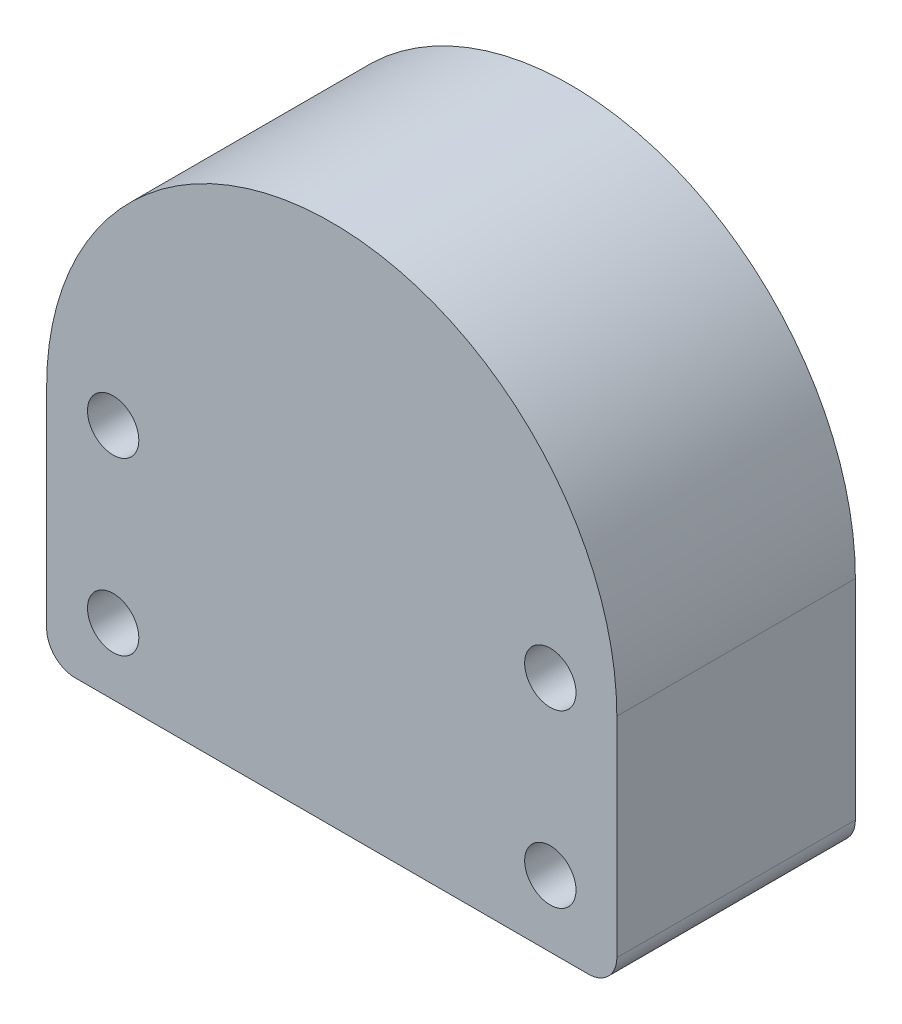
SolidWorks part; units mm, degrees
ref_plane "Front Plane" through (0, 0, 0) normal (0, 0, 1) x (1, 0, 0)
ref_plane "Top Plane" through (0, 0, 0) normal (0, 1, 0) x (1, 0, 0)
ref_plane "Right Plane" through (0, 0, 0) normal (1, 0, 0) x (0, 0, -1)
sketch "Sketch1" plane through (0, 0, 0) normal (0, 0, 1) x (1, 0, 0)
  line L1 (38.9055, 72) -> (38.9055, 47)
  line L4 (-21.0945, 72) -> (-21.0945, 47)
  line L6 (38.9055, 47) -> (-21.0945, 47)
  arc A2 (38.9055, 72) -> (-21.0945, 72) centre (8.9055, 72) ccw
extrude "Boss-Extrude1" add sketch "Sketch1" along normal blind 25.1
hole_wizard "M5 Clearance Hole1" positions "Sketch2" profile "Sketch3" hole size "M5" standard "ISO" end condition through all
sketch "Sketch2" plane through (0, 0, 25.1) normal (0, 0, -1) x (-1, 0, 0)
  point P0 (-31.9055, 72)
  point P2 (-31.9055, 54)
  point P4 (14.0945, 54)
  point P6 (14.0945, 72)
sketch "Sketch3" plane through (31.9055, 72, 25.1) normal (1, 0, 0) x (0, -1, 0)
  line L0 (0, 0) -> (0, 25.1)
  line L1 (0, 25.1) -> (2.7, 25.1)
  line L2 (2.7, 25.1) -> (2.7, 0)
  line L5 (2.7, 0) -> (0, 0)
  line L11 (0, -6.35) -> (0, 107.95) construction
  dimension "Thru Hole Dia." = 5.4
  dimension "Thru Hole Depth" = 25.1
fillet "Fillet1" radius 3 2 edges at (38.9055, 47, 12.55) (-21.0945, 47, 12.55)
